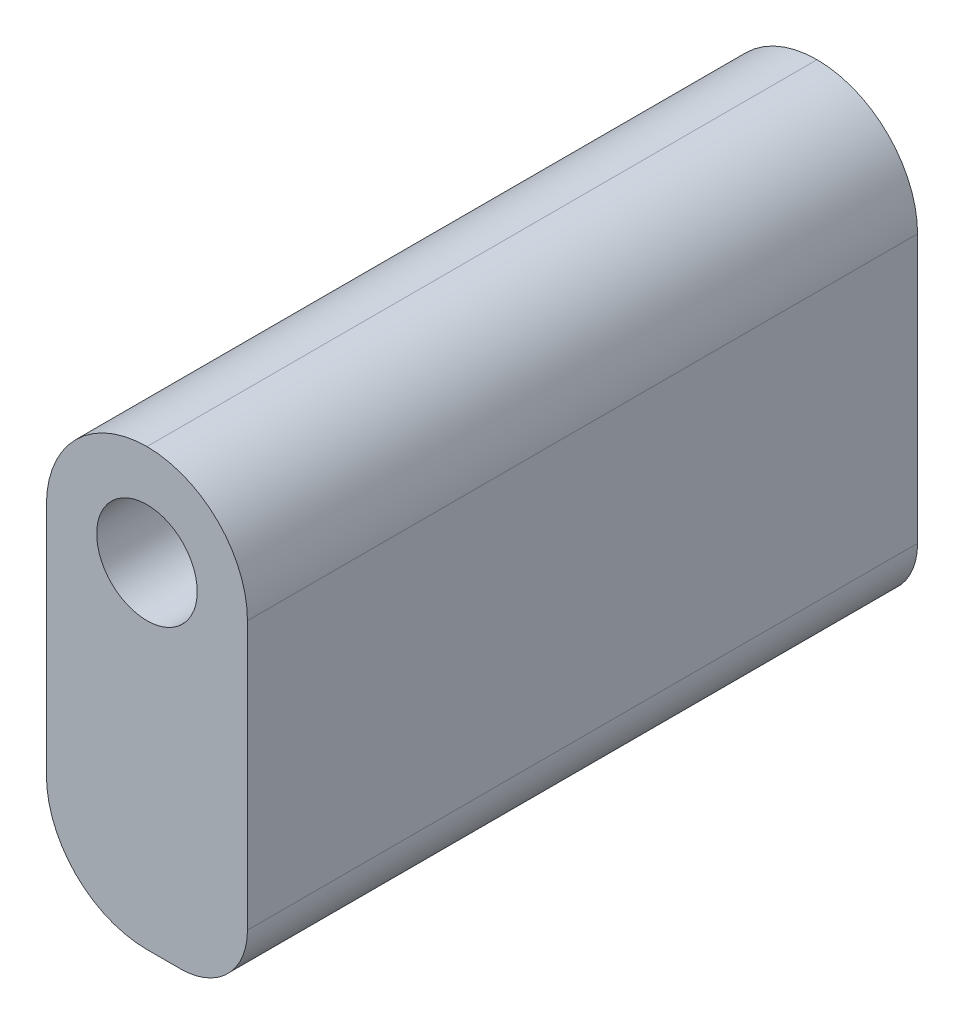
SolidWorks part; units mm, degrees
ref_plane "Front Plane" through (0, 0, 0) normal (0, 0, 1) x (1, 0, 0)
ref_plane "Top Plane" through (0, 0, 0) normal (0, 1, 0) x (1, 0, 0)
ref_plane "Right Plane" through (0, 0, 0) normal (1, 0, 0) x (0, 0, -1)
sketch "Sketch1" plane through (0, 0, 0) normal (0, 0, 1) x (1, 0, 0)
  line L4 (0, 0) -> (0, 6) construction
  line L7 (-6, 6) -> (6, 6)
  line L8 (-6, 6) -> (-6, -20)
  line L18 (-6, -20) -> (6, -20)
  line L19 (6, -20) -> (6, 6)
  circle A7 centre (0, 0) radius 3
  dimension "D1" = 20
  dimension "D8" = 6
  dimension "D2" = 12
  dimension "D7" = 6
extrude "Boss-Extrude1" add sketch "Sketch1" along normal mid plane 40
fillet "Fillet1" radius 6 3 edges at (-6, -20, 0) (6, 6, 0) (-6, 6, 0)
fillet "Fillet2" radius 4 1 edges at (6, -20, 0)
